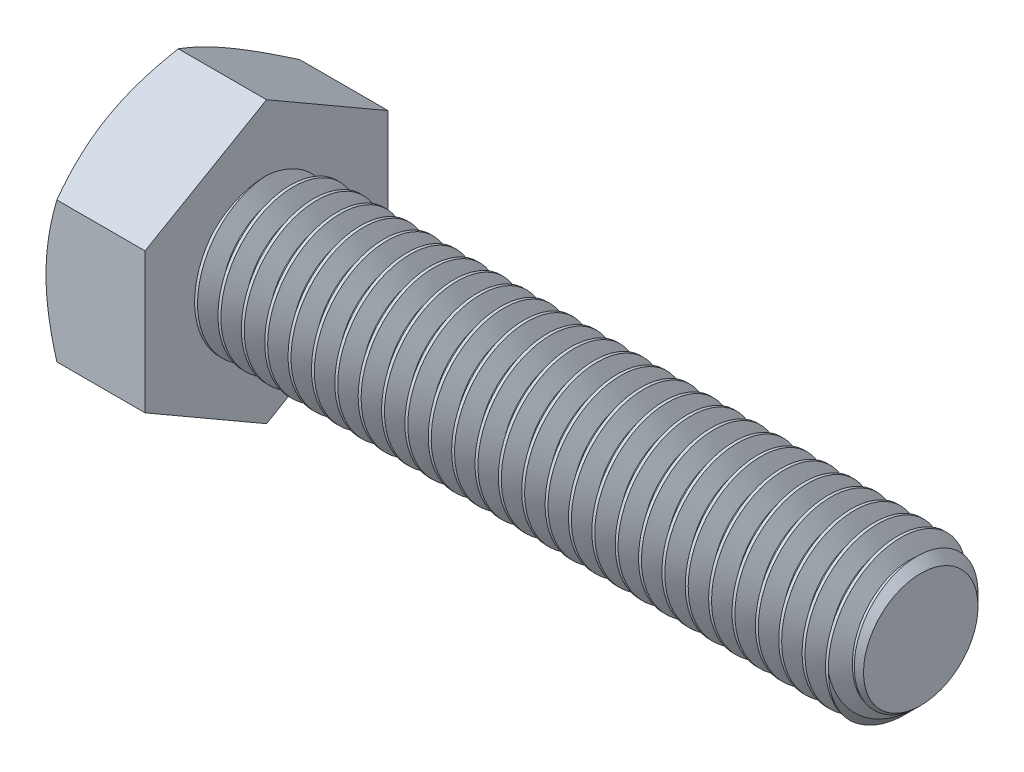
SolidWorks part; units mm, degrees
ref_plane "Front Plane" through (0, 0, 0) normal (0, 0, 1) x (1, 0, 0)
ref_plane "Top Plane" through (0, 0, 0) normal (0, 1, 0) x (1, 0, 0)
ref_plane "Right Plane" through (0, 0, 0) normal (1, 0, 0) x (0, 0, -1)
sketch "Sketch1" plane through (0, 0, 0) normal (0, 0, 1) x (1, 0, 0)
  line L0 (-20.15, 0) -> (20.15, 0) construction
  line L1 (-14.85, 6.5) -> (-14.85, -6.5) construction
  line L2 (-20.15, 6.5) -> (-20.15, -6.5) construction
  line L3 (20.15, 4) -> (20.15, -4) construction
  point P8 (15.775, -4)
  dimension "Thread Dia" = 8
  dimension "Hex" = 13
  dimension "Head Ht" = 5.3
  dimension "Length" = 35
  dimension "D1" = 4.375
ref_plane "Plane2" through (20.15, 0, 0) normal (1, 0, 0) x (0, 0, -1)
sketch "Sketch2" plane through (20.15, 0, 0) normal (1, 0, 0) x (0, 0, -1)
  circle A0 centre (0, 0) radius 4
extrude "Boss-Extrude1" add sketch "Sketch2" against normal up to vertex (35 mm away) up to point (-14.85, -6.5, 0)
sketch "Sketch4" plane through (20.15, 0, 0) normal (1, 0, 0) x (0, 0, -1)
  circle A1 centre (0, 0) radius 4
  circle A2 centre (0, 0) radius 4
  dimension "D1" = 0
curve "Helix/Spiral1" pitch 1.25 height 36.25 turns 29 parameters "Pitch"=1.25
chamfer "Chamfer1" distance 0.9375 angle 45 1 edges at (20.15, 0, -4)
sketch "Sketch5" plane through (0, 0, 0) normal (0, 0, 1) x (1, 0, 0)
  line L0 (20.15, 4) -> (20.6187, 3.1881)
  line L1 (20.6187, 3.1881) -> (20.775, 3.1881)
  line L2 (20.775, 3.1881) -> (21.2437, 4)
  line L3 (20.15, 4) -> (21.2437, 4)
  line L4 (20.6969, 3.1881) -> (20.6969, 4) construction
  line L5 (20.3844, 3.5941) -> (21.0094, 3.5941) construction
  line L6 (20.15, -4) -> (20.15, 4) construction
  dimension "D1" = 60
  dimension "D2" = 0.1562
  dimension "D3" = 0.625
sweep "Cut-Sweep1" cut profiles "Sketch5" path "Helix/Spiral1"
sketch "Sketch3" plane through (-14.85, 0, 0) normal (-1, 0, 0) x (0, 0, 1)
  line L0 (0, 6.5) -> (0, -6.5) construction
  line L1 (-6.5, -3.7528) -> (0, -7.5056)
  line L2 (0, -7.5056) -> (6.5, -3.7528)
  line L3 (6.5, -3.7528) -> (6.5, 3.7528)
  line L4 (6.5, 3.7528) -> (0, 7.5056)
  line L5 (0, 7.5056) -> (-6.5, 3.7528)
  line L6 (-6.5, 3.7528) -> (-6.5, -3.7528)
  circle A0 centre (0, 0) radius 6.5 construction
extrude "Boss-Extrude2" add sketch "Sketch3" along normal up to vertex (5.3 mm away) up to point (-20.15, -6.5, 0)
sketch "Sketch6" plane through (-20.15, 0, 0) normal (-1, 0, 0) x (0, 0, 1)
  circle A0 centre (0, 0) radius 6.5 construction
  circle A1 centre (0, 0) radius 6.5
extrude "Cut-Extrude1" cut sketch "Sketch6" against normal through all draft 60 flip side to cut
sketch "Sketch9" plane through (0, 0, 0) normal (0, 0, 1) x (1, 0, 0)
  line L0 (-14.85, 4) -> (-14.85, 0)
  line L1 (-14.85, 0) -> (6.15, 0)
  line L2 (6.15, 0) -> (2.15, 4)
  line L3 (2.15, 4) -> (-14.85, 4)
  line L4 (-20.15, 0) -> (20.15, 0) construction
  line L5 (-14.85, 6.5) -> (-14.85, -6.5) construction
  line L6 (20.15, 4) -> (20.15, -4) construction
  dimension "D1" = 45
  dimension "MinThreadLg" = 18
revolve "Revolve1" [suppressed] add sketch "Sketch9" angle 360 about L1
equation "\"D2@Sketch5\" = \"Pitch@Helix/Spiral1\"*.125"
equation "\"D3@Sketch5\" = \"Pitch@Helix/Spiral1\"*.50"
equation "\"D3@Helix/Spiral1\" = \"Length@Sketch1\"+\"Pitch@Helix/Spiral1\""
equation "\"D1@Chamfer1\" = \"Pitch@Helix/Spiral1\"*.750"
equation "\"D1@Sketch1\" = \"Pitch@Helix/Spiral1\"*3.50"
